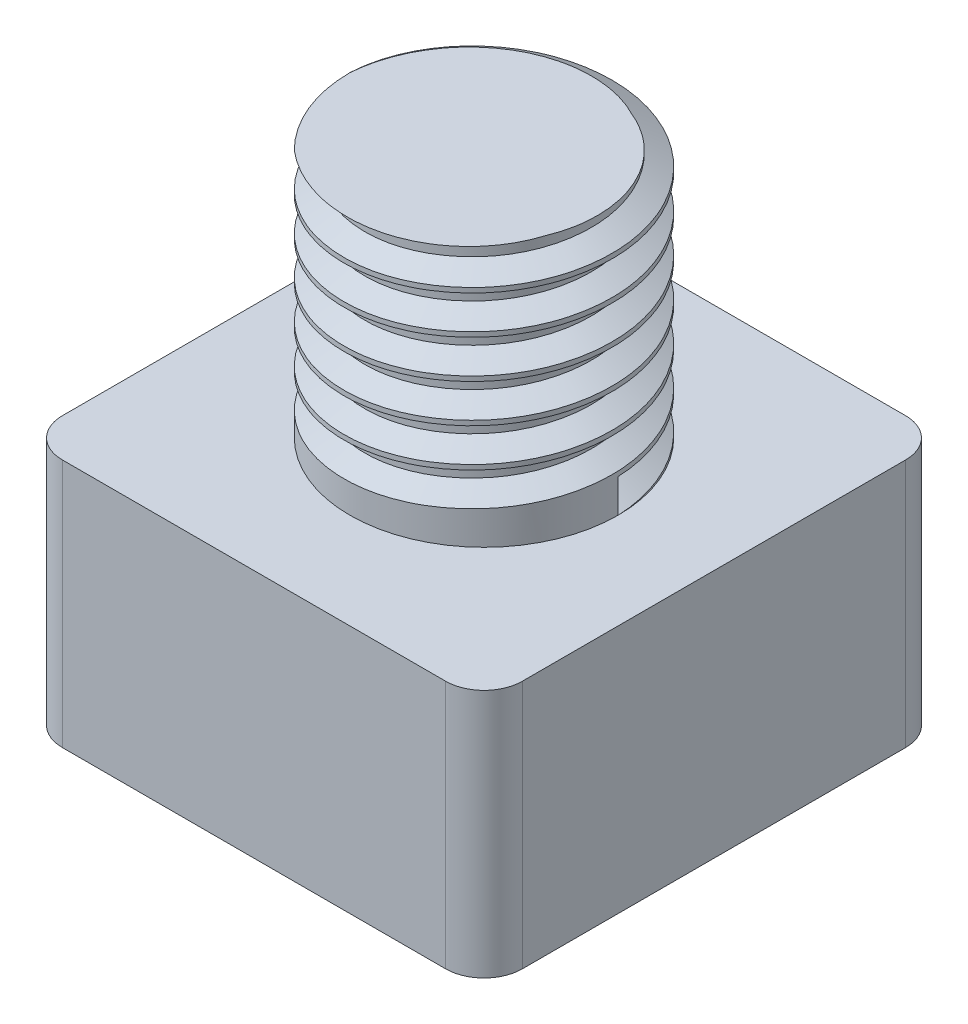
SolidWorks part; units mm, degrees
ref_plane "Front Plane" through (0, 0, 0) normal (0, 0, 1) x (1, 0, 0)
ref_plane "Top Plane" through (0, 0, 0) normal (0, 1, 0) x (1, 0, 0)
ref_plane "Right Plane" through (0, 0, 0) normal (1, 0, 0) x (0, 0, -1)
sketch "Sketch1" plane through (0, 0, 0) normal (0, 1, 0) x (1, 0, 0)
  line L1 (-6, -6) -> (6, -6)
  line L2 (-6, -6) -> (-6, 6)
  line L3 (-6, 6) -> (6, 6)
  line L4 (6, -6) -> (6, 6)
  line L5 (-6, -6) -> (6, 6) construction
  line L6 (-6, 6) -> (6, -6) construction
  point P0 (0, 0)
  dimension "D1" = 12
extrude "Boss-Extrude1" add sketch "Sketch1" along normal blind 6.5
sketch "Sketch2" plane through (0, 6.5, 0) normal (0, 1, 0) x (1, 0, 0)
  circle A0 centre (0, 0) radius 3.5
  dimension "D1" = 7
extrude "Boss-Extrude2" add sketch "Sketch2" along normal blind 6.5
thread "Thread1" pitch 1 method cut profile "Thread Profile1" start angle 0, offset 0, length 10, pitch 1, diameter 7
ref_plane "Plane1" through (3.5, 6.5, 0) normal (0, 0, 1) x (1, 0, 0)
sketch "Thread Profile1" plane through (3.5, 6.5, 0) normal (0, 0, 1) x (1, 0, 0)
  line L0 (0, 0) -> (0, 1) construction
  line L11 (0, 0) -> (0, 0.875)
  line L12 (0, 0.875) -> (-0.5413, 0.5625)
  line L13 (-0.5413, 0.5625) -> (-0.5413, 0.3125)
  line L15 (-0.5413, 0.3125) -> (0, 0)
  line L17 (-0.5413, 0.4375) -> (0, 0.4375) construction
  point P2 (0, 0)
  dimension "Pitch" = 1
  dimension "Profile_Angle" = 60
  dimension "Profile_Land" = 0.25
  dimension "Profile_Height" = 0.5413
fillet "Fillet1" radius 1 4 edges at (-6, 3.25, -6) (6, 3.25, -6) (6, 3.25, 6) (-6, 3.25, 6)
